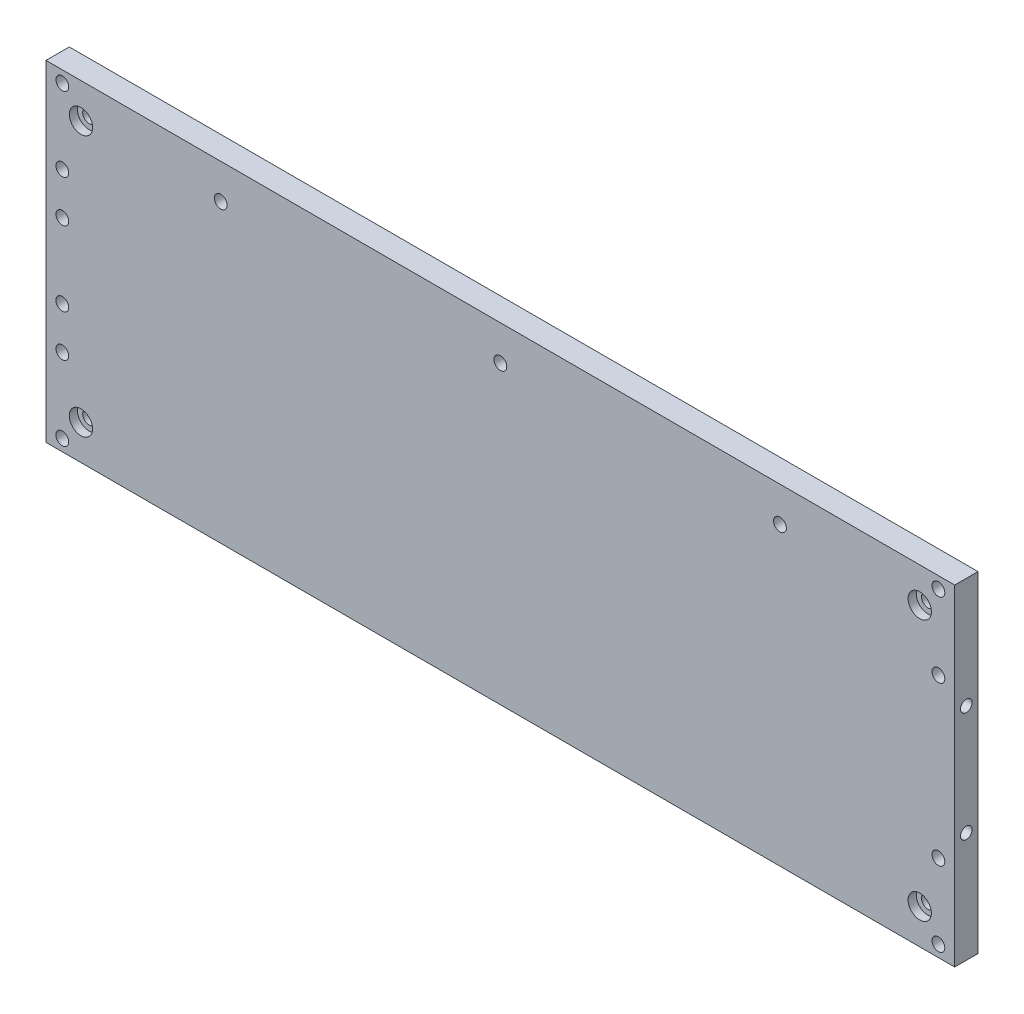
SolidWorks part; units mm, degrees
ref_plane "Front Plane" through (0, 0, 0) normal (0, 0, 1) x (1, 0, 0)
ref_plane "Top Plane" through (0, 0, 0) normal (0, 1, 0) x (1, 0, 0)
ref_plane "Right Plane" through (0, 0, 0) normal (1, 0, 0) x (0, 0, -1)
sketch "Sketch1" plane through (0, 0, 0) normal (0, 0, 1) x (1, 0, 0)
  line L1 (195, -71) -> (-195, -71)
  line L2 (195, -71) -> (195, 71)
  line L3 (195, 71) -> (-195, 71)
  line L4 (-195, -71) -> (-195, 71)
  line L5 (195, -71) -> (-195, 71) construction
  line L6 (195, 71) -> (-195, -71) construction
  point P0 (0, 0)
  dimension "D1" = 390
  dimension "D2" = 142
extrude "Boss-Extrude1" add sketch "Sketch1" along normal mid plane 10
sketch "Sketch2" plane through (0, 0, -5) normal (0, 0, -1) x (-1, 0, 0)
  line L0 (-188, 71) -> (-188, -71) construction
  line L1 (-195, 71) -> (195, 71) construction
  line L2 (195, -71) -> (-195, -71) construction
  line L3 (-195, -71) -> (-195, 71) construction
  line L4 (188, 71) -> (188, -71) construction
  line L5 (195, 71) -> (195, -71) construction
  line L6 (-195, 66) -> (195, 66) construction
  line L7 (-195, -66) -> (195, -66) construction
  line L8 (-195, 34) -> (195, 34) construction
  line L9 (-195, -34) -> (195, -34) construction
  circle A0 centre (-188, 66) radius 2.75
  circle A1 centre (-188, -66) radius 2.75
  circle A2 centre (188, 66) radius 2.75
  circle A3 centre (188, -66) radius 2.75
  circle A4 centre (-188, 34) radius 2.75
  circle A5 centre (-188, -34) radius 2.75
  circle A6 centre (188, 34) radius 2.75
  circle A7 centre (188, -34) radius 2.75
  dimension "D5" = 5.5
  dimension "D6" = 5.5
  dimension "D7" = 5.5
  dimension "D8" = 5.5
  dimension "D11" = 5.5
  dimension "D12" = 5.5
  dimension "D13" = 5.5
  dimension "D14" = 5.5
  dimension "D1" = 7
  dimension "D2" = 7
  dimension "D3" = 5
  dimension "D4" = 5
  dimension "D9" = 32
  dimension "D10" = 32
extrude "Cut-Extrude1" cut sketch "Sketch2" against normal through all
sketch "Sketch3" plane through (0, 0, 5) normal (0, 0, 1) x (1, 0, 0)
  line L0 (-195, 56) -> (195, 56) construction
  line L1 (-195, 71) -> (-195, -71) construction
  line L2 (195, -71) -> (195, 71) construction
  line L3 (-195, -56) -> (195, -56) construction
  line L4 (-180, 71) -> (-180, -71) construction
  line L5 (195, 71) -> (-195, 71) construction
  line L6 (-195, -71) -> (195, -71) construction
  line L7 (180, 71) -> (180, -71) construction
  line L8 (-120, 71) -> (-120, -71) construction
  line L9 (120, 71) -> (120, -71) construction
  circle A0 centre (-180, 56) radius 2.75
  circle A1 centre (180, 56) radius 2.75
  circle A2 centre (180, -56) radius 2.75
  circle A3 centre (-180, -56) radius 2.75
  circle A4 centre (0, 56) radius 2.75
  circle A5 centre (-120, 56) radius 2.75
  circle A6 centre (120, 56) radius 2.75
  dimension "D5" = 5.5
  dimension "D6" = 5.5
  dimension "D7" = 5.5
  dimension "D8" = 5.5
  dimension "D9" = 5.5
  dimension "D12" = 5.5
  dimension "D13" = 5.5
  dimension "D1" = 15
  dimension "D2" = 15
  dimension "D3" = 15
  dimension "D4" = 15
  dimension "D10" = 75
  dimension "D11" = 75
extrude "Cut-Extrude2" cut sketch "Sketch3" against normal through all
sketch "Sketch4" plane through (0, 0, 5) normal (0, 0, 1) x (1, 0, 0)
  circle A0 centre (-180, 56) radius 5
  circle A1 centre (-180, -56) radius 5
  circle A2 centre (180, 56) radius 5
  circle A3 centre (180, -56) radius 5
  dimension "D1" = 10
  dimension "D2" = 10
  dimension "D3" = 10
  dimension "D4" = 10
extrude "Cut-Extrude3" cut sketch "Sketch4" against normal blind 3.5
sketch "Sketch5" plane through (195, 0, 0) normal (1, 0, 0) x (0, 0, -1)
  line L0 (0, 71) -> (0, -71) construction
  line L1 (-5, 71) -> (5, 71) construction
  line L2 (-5, -71) -> (5, -71) construction
  circle A0 centre (0, 23.6) radius 2.5
  circle A1 centre (0, -23.6) radius 2.5
  dimension "D1" = 5
  dimension "D2" = 5
  dimension "D3" = 23.6
  dimension "D4" = 23.6
extrude "Cut-Extrude4" cut sketch "Sketch5" against normal blind 10
sketch "Sketch6" plane through (0, 0, 5) normal (0, 0, 1) x (1, 0, 0)
  line L0 (-188, 34) -> (-188, -34) construction
  line L1 (-188, 0) -> (195, 0) construction
  line L2 (195, -71) -> (195, 71) construction
  circle A0 centre (-188, 16) radius 2.75
  circle A1 centre (-188, -16) radius 2.75
  circle A2 centre (-188, 34) radius 2.75 construction
  dimension "D1" = 16
  dimension "D3" = 5.5
  dimension "D4" = 5.5
  dimension "D2" = 16
extrude "Cut-Extrude5" cut sketch "Sketch6" against normal through all
equation "\"D3@Sketch5\"=47.2/2"
equation "\"D4@Sketch5\"=47.2/2"
equation "\"D1@Sketch6\"=32/2"
equation "\"D2@Sketch6\"=32/2"
